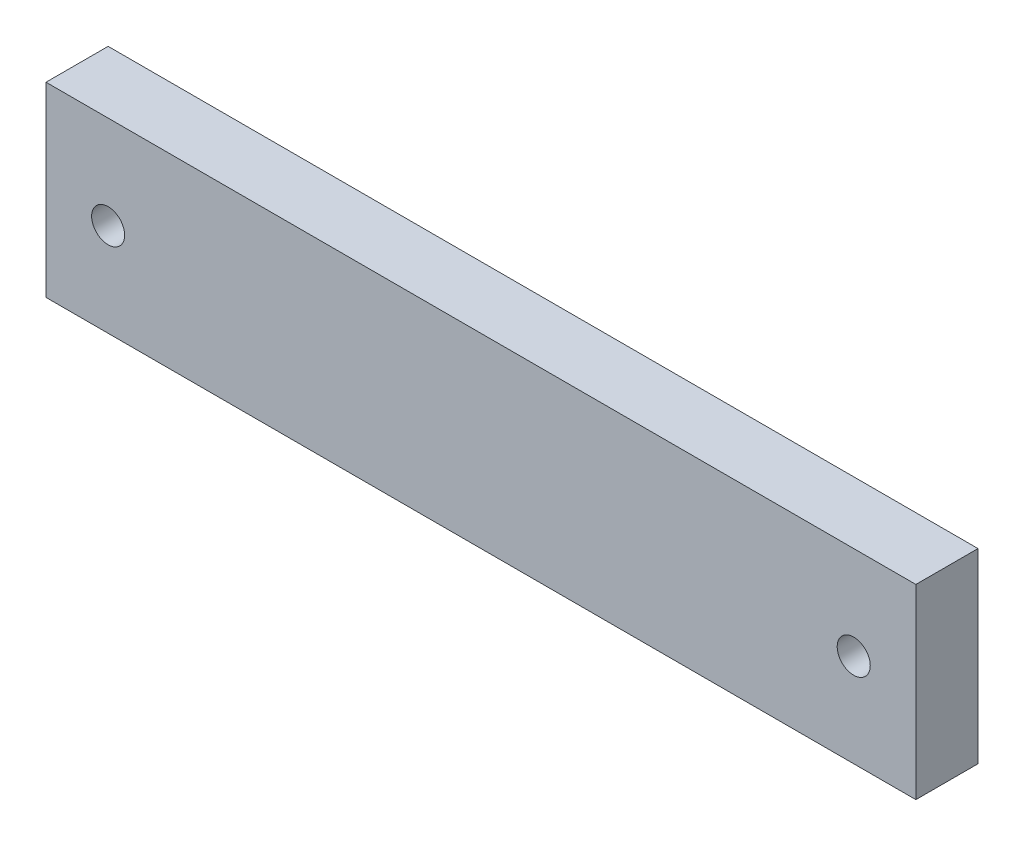
SolidWorks part; units mm, degrees
material "Plain Carbon Steel"
ref_plane "Front Plane" through (0, 0, 0) normal (0, 0, 1) x (1, 0, 0)
ref_plane "Top Plane" through (0, 0, 0) normal (0, 1, 0) x (1, 0, 0)
ref_plane "Right Plane" through (0, 0, 0) normal (1, 0, 0) x (0, 0, -1)
sketch "Sketch1" plane through (0, 0, 0) normal (0, 0, 1) x (1, 0, 0)
  line L1 (0, 0) -> (177.8, 0)
  line L2 (0, 0) -> (0, 38.1)
  line L3 (0, 38.1) -> (177.8, 38.1)
  line L4 (177.8, 0) -> (177.8, 38.1)
  dimension "D1" = 38.1
  dimension "D2" = 177.8
extrude "Boss-Extrude1" add sketch "Sketch1" along normal blind 12.7
hole_wizard "1/4 Clearance Hole1" positions "Sketch2" profile "Sketch3" hole size "1/4" standard "ANSI Inch" end condition through all
sketch "Sketch2" plane through (0, 0, 12.7) normal (0, 0, 1) x (1, 0, 0)
  line L0 (88.9, 38.1) -> (88.9, 0) construction
  line L1 (177.8, 38.1) -> (0, 38.1) construction
  line L2 (0, 0) -> (177.8, 0) construction
  line L3 (0, 19.05) -> (177.8, 19.05) construction
  line L4 (0, 38.1) -> (0, 0) construction
  line L5 (177.8, 0) -> (177.8, 38.1) construction
  point P0 (12.7, 19.05)
  point P10 (165.1, 19.05)
  dimension "D1" = 152.4
sketch "Sketch3" plane through (12.7, 19.05, 12.7) normal (1, 0, 0) x (0, -1, 0)
  line L0 (0, 0) -> (0, 12.7)
  line L1 (0, 12.7) -> (3.3782, 12.7)
  line L2 (3.3782, 12.7) -> (3.3782, 0)
  line L5 (3.3782, 0) -> (0, 0)
  line L11 (0, -6.35) -> (0, 107.95) construction
  dimension "Thru Hole Dia." = 6.7564
  dimension "Thru Hole Depth" = 12.7
